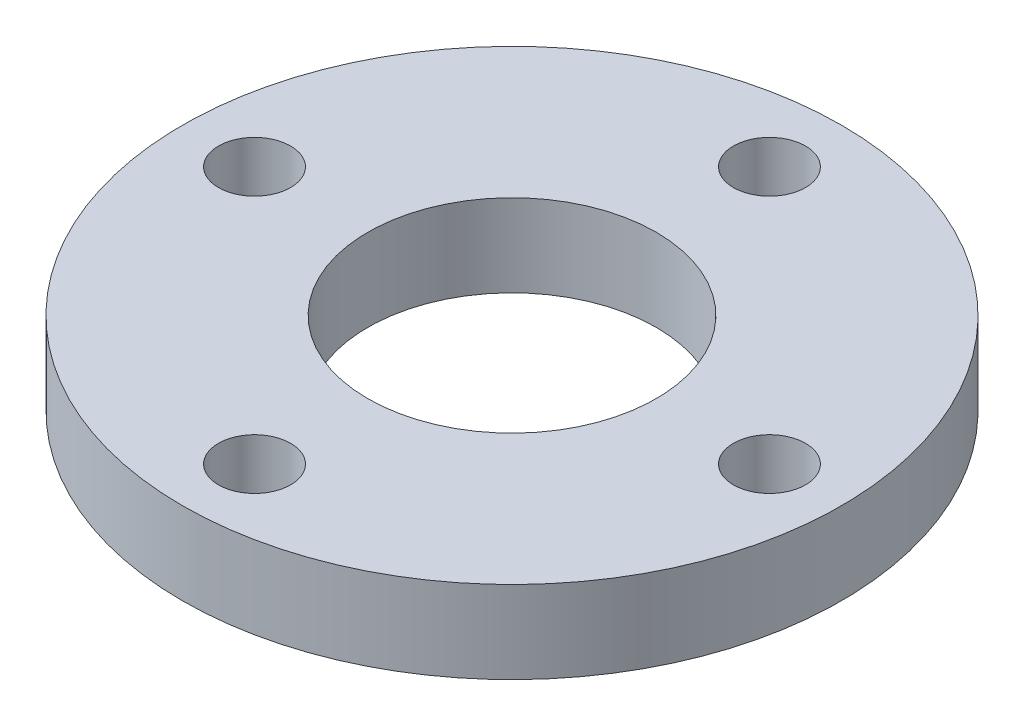
SolidWorks part; units mm, degrees
ref_plane "Front Plane" through (0, 0, 0) normal (0, 0, 1) x (1, 0, 0)
ref_plane "Top Plane" through (0, 0, 0) normal (0, 1, 0) x (1, 0, 0)
ref_plane "Right Plane" through (0, 0, 0) normal (1, 0, 0) x (0, 0, -1)
sketch "Sketch1" plane through (0, 0, 0) normal (0, 1, 0) x (1, 0, 0)
  circle A0 centre (0, 0) radius 16
  circle A1 centre (0, 0) radius 7
  circle A2 centre (0, 0) radius 12.5 construction
  circle A3 centre (0, 12.5) radius 1.75
  circle A4 centre (12.5, 0) radius 1.75
  circle A5 centre (0, -12.5) radius 1.75
  circle A6 centre (-12.5, 0) radius 1.75
  point P16 (0, 0)
  dimension "D1" = 32
  dimension "D2" = 14
  dimension "D3" = 3.5
  dimension "D5" = 25
  dimension "D4" = 4
extrude "Boss-Extrude1" add sketch "Sketch1" along normal blind 4
